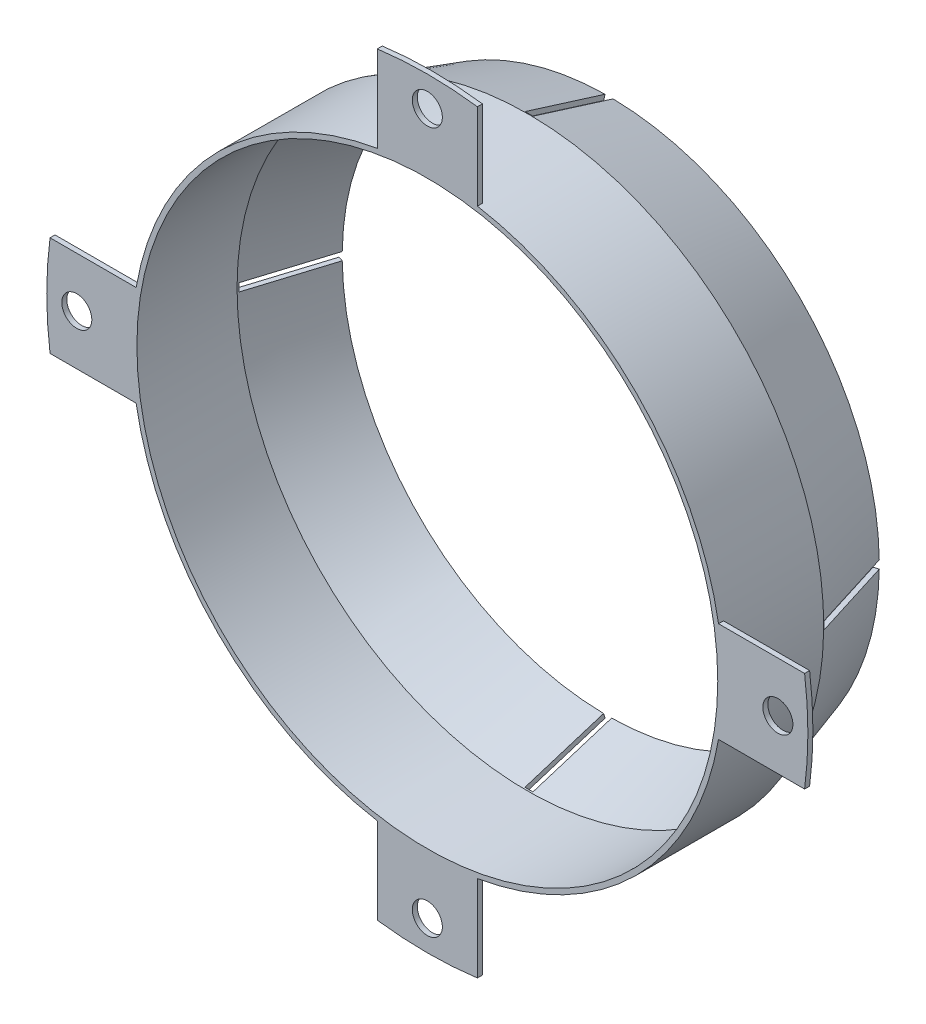
SolidWorks part; units mm, degrees
material "AISI Type 316L stainless steel"
ref_plane "Front Plane" through (0, 0, 0) normal (0, 0, 1) x (1, 0, 0)
ref_plane "Top Plane" through (0, 0, 0) normal (0, 1, 0) x (1, 0, 0)
ref_plane "Right Plane" through (0, 0, 0) normal (1, 0, 0) x (0, 0, -1)
sketch "Sketch1" plane through (0, 0, 0) normal (1, 0, 0) x (0, 0, -1)
  line L0 (0, 0) -> (-57.6633, 0) construction
  line L1 (0, 38) -> (0, 29)
  line L2 (0, 29) -> (10, 29)
  line L3 (10, 29) -> (18, 26.5)
  dimension "D1" = 58
  dimension "D2" = 76
  dimension "D3" = 53
  dimension "D4" = 10
  dimension "D5" = 18
revolve "Revolve-Thin1" add sketch "Sketch1" angle 360 about L0 wall 0.5
sketch "Sketch2" plane through (0, 0, -0.5) normal (0, 0, -1) x (-1, 0, 0)
  line L0 (0, 0) -> (0, 40.3707) construction
  line L1 (-5, 37.6696) -> (-5, 29.0732)
  line L2 (-50.3656, 0) -> (0, 0) construction
  line L3 (-37.6696, 5) -> (-29.0732, 5)
  circle A0 centre (0, 0) radius 38 construction
  circle A1 centre (0, 0) radius 29.5 construction
  circle A2 centre (0, 0) radius 29.5 construction
  arc A3 (-5, 37.6696) -> (-37.6696, 5) centre (0, 0) ccw
  arc A4 (-5, 29.0732) -> (-29.0732, 5) centre (0, 0) ccw
  dimension "D1" = 10
  dimension "D2" = 10
extrude "Cut-Extrude1" cut sketch "Sketch2" against normal blind 10
ref_axis "Axis1" through (0, 0, -19.0566) along (0, 0, 1)
hole_wizard "Ø3.0 (3) Diameter Hole1" positions "Sketch4" profile "Sketch3" hole size "Ø3.0" standard "Ansi Metric"
sketch "Sketch4" plane through (0, 0, -0.5) normal (0, 0, -1) x (-1, 0, 0)
  point P0 (0, 35)
  dimension "D1" = 35
sketch "Sketch3" plane through (0, 35, -0.5) normal (1, 0, 0) x (0, 1, 0)
  line L0 (0, 0) -> (0, 23.9013)
  line L1 (0, 23.9013) -> (1.5, 23)
  line L2 (1.5, 23) -> (1.5, 0)
  line L5 (1.5, 0) -> (0, 0)
  line L10 (0, 23.9013) -> (-1.5, 23) construction
  line L11 (0, -6.35) -> (0, 107.95) construction
  dimension "Hole Dia." = 3
  dimension "Hole Depth" = 23
  dimension "Drill Angle" = 118
sketch "Sketch5" plane through (0, 0, 0) normal (0, 1, 0) x (1, 0, 0)
  line L0 (0, 0) -> (0, 28.3829) construction
  line L1 (-0.4, 18.1491) -> (0.4, 18.1491)
  line L2 (-0.4, 18.1491) -> (-0.4, 10.1481)
  line L3 (-0.4, 10.1481) -> (0.4, 10.1481)
  line L4 (0.4, 18.1491) -> (0.4, 10.1481)
  line L5 (0, 19.0566) -> (0, -0.9075) construction
  line L6 (-26.9772, 18.1491) -> (26.9772, 18.1491) construction
  dimension "D1" = 0.8
  dimension "D2" = 8.001
extrude "Cut-Extrude2" cut sketch "Sketch5" against normal through all
pattern_circular "CirPattern1" count 4 over 360 about axis through (0, 0, -19.0566) along (0, 0, 1) of "Cut-Extrude1", "Ø3.0 (3) Diameter Hole1", "Cut-Extrude2"
